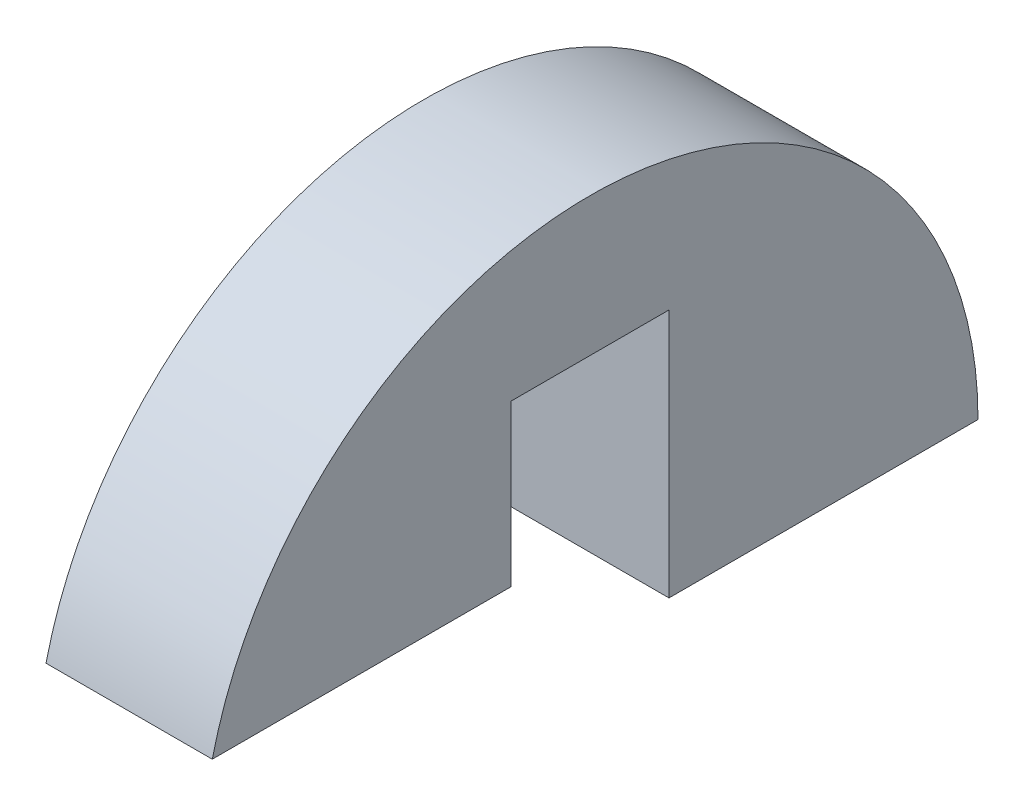
SolidWorks part; units mm, degrees
ref_plane "Front Plane" through (0, 0, 0) normal (0, 0, 1) x (1, 0, 0)
ref_plane "Top Plane" through (0, 0, 0) normal (0, 1, 0) x (1, 0, 0)
ref_plane "Right Plane" through (0, 0, 0) normal (1, 0, 0) x (0, 0, -1)
sketch "Sketch2" plane through (0, 0, 0) normal (0, 1, 0) x (1, 0, 0)
  line L0 (1.6, 1.425) -> (0, 1.425)
  line L1 (0, 1.425) -> (0, 7)
  line L5 (1.6, 6.8147) -> (1.6, 1.425)
  line L6 (1.6, 1.425) -> (4.5, 1.425)
  line L7 (4.5, 1.425) -> (4.5, -1.425)
  line L8 (4.5, -1.425) -> (1.6, -1.425)
  line L9 (1.6, -1.425) -> (1.6, -6.8147)
  line L10 (1.6, 6.8147) -> (1.6, 1.425) construction
  line L11 (1.6, 1.425) -> (4.5, 1.425)
  line L12 (4.5, 1.425) -> (4.5, -1.425)
  line L13 (4.5, -1.425) -> (1.6, -1.425)
  line L14 (1.6, -1.425) -> (1.6, -6.8147)
  arc A0 (1.6, 6.8147) -> (0, 7) centre (0, 0) ccw
  arc A1 (1.6, -6.8147) -> (1.6, 6.8147) centre (0, 0) ccw
  arc A2 (1.6, -6.8147) -> (1.6, 6.8147) centre (0, 0) ccw
  dimension "D1" = 0
extrude "Boss-Extrude1" add sketch "Sketch2" along normal blind 1.5 and the other way blind 1.5
ref_axis "Axis1" through (0, 0, -7.6907) along (0, 0, 1)
move or copy body "Body-Move/Copy1" bodies to move or copy 101 copy no rotation origin (0, 0, 0) rotation axis (0, 0, 1) rotation angle 90
